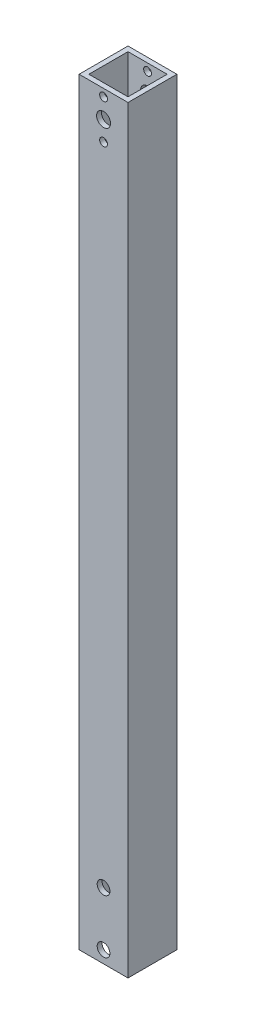
SolidWorks part; units mm, degrees
material "Gerais  - 6061-T6"
ref_plane "Plano frontal" through (0, 0, 0) normal (0, 0, 1) x (1, 0, 0)
ref_plane "Plano superior" through (0, 0, 0) normal (0, 1, 0) x (1, 0, 0)
ref_plane "Plano direito" through (0, 0, 0) normal (1, 0, 0) x (0, 0, -1)
sketch "Esboço1" plane through (0, 0, 0) normal (0, 1, 0) x (1, 0, 0)
  line L1 (0, 0) -> (20, 0)
  line L2 (0, 0) -> (0, 20)
  line L3 (0, 20) -> (20, 20)
  line L4 (20, 0) -> (20, 20)
  dimension "D1" = 20
extrude "Extrusão-Fina1" add sketch "Esboço1" along normal blind 310 thin thin type one direction reverse wall 2
sketch "Esboço4" plane through (0, 0, 0) normal (0, 0, 1) x (1, 0, 0)
  line L0 (10, 307) -> (10, 291) construction
  line L1 (0, 310) -> (20, 310) construction
  circle A0 centre (10, 299) radius 2.85
  circle A1 centre (10, 291) radius 1.6
  circle A2 centre (10, 307) radius 1.6
  circle A3 centre (10, 299) radius 11 construction
  point P8 (10, 310)
  dimension "D1" = 3.2
  dimension "D2" = 5.7
  dimension "D4" = 22
  dimension "D3" = 16
extrude "Corte-extrusão2" cut sketch "Esboço4" against normal through all
sketch "Esboço5" plane through (0, 0, -20) normal (0, 0, -1) x (-1, 0, 0)
  circle A2 centre (-10, 5) radius 2.6
  circle A3 centre (-10, 27) radius 2.6
extrude "Corte-extrusão5" cut sketch "Esboço5" against normal through all
